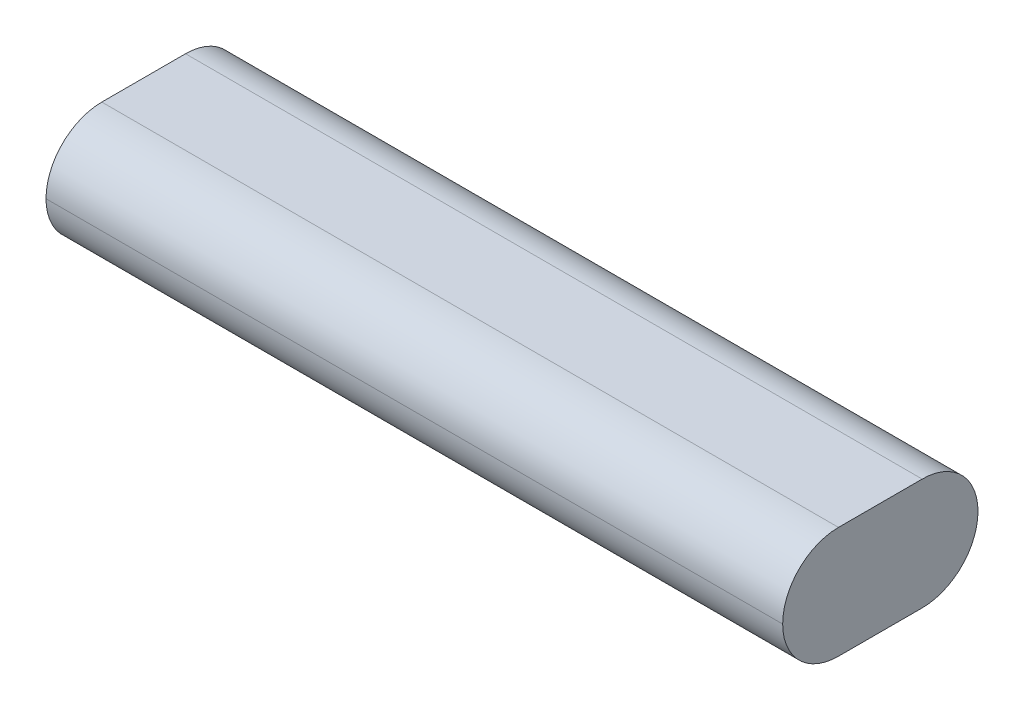
SolidWorks part; units mm, degrees
ref_plane "Front Plane" through (0, 0, 0) normal (0, 0, 1) x (1, 0, 0)
ref_plane "Top Plane" through (0, 0, 0) normal (0, 1, 0) x (1, 0, 0)
ref_plane "Right Plane" through (0, 0, 0) normal (1, 0, 0) x (0, 0, -1)
sketch "Sketch2" plane through (0, 0, 0) normal (0, 1, 0) x (1, 0, 0)
  line L1 (-87.7695, -5.2707) -> (44.2305, -5.2707)
  line L2 (-87.7695, -5.2707) -> (-87.7695, -40.2707)
  line L3 (-87.7695, -40.2707) -> (44.2305, -40.2707)
  line L4 (44.2305, -5.2707) -> (44.2305, -40.2707)
extrude "Boss-Extrude1" add sketch "Sketch2" along normal blind 20
fillet "Fillet1" radius 10 4 edges at (-21.7695, 0, 40.2707) (-21.7695, 0, 5.2707) (-21.7695, 20, 5.2707) (-21.7695, 20, 40.2707)
